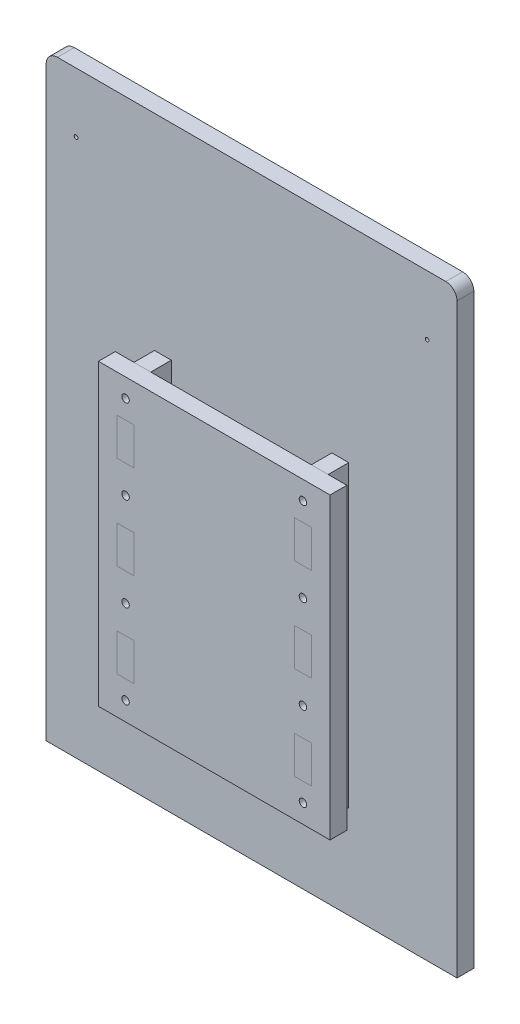
SolidWorks part; units mm, degrees
note: The reader was unsure of these and kept them because the rebuilt part matched: shared geometry of "Model<3>", "Model<4>", "Model<5>", "Model<7>", "Model<8>", "Model<9>".
other "volet-fond"
other "volet_plauqeDessus"
other "voletSupportD"
other "volet-supportG"
ref_plane "Plan de face" through (0, 0, 0) normal (0, 0, 1) x (1, 0, 0)
ref_plane "Plan de dessus" through (0, 0, 0) normal (0, 1, 0) x (1, 0, 0)
ref_plane "Plan de droite" through (0, 0, 0) normal (1, 0, 0) x (0, 0, -1)
sketch "Model" plane through (0, 0, 0) normal (0, 0, 1) x (1, 0, 0)
  line L0 (0, 320) -> (-104, 320)
  line L1 (-110, 314) -> (-110, 0)
  line L2 (-110, 0) -> (0, 0)
  line L3 (0, 0) -> (110, 0)
  line L4 (110, 0) -> (110, 314)
  line L5 (104, 320) -> (0, 320)
  line L6 (-52, 190) -> (-52, 170)
  line L7 (-52, 170) -> (-43, 170)
  line L8 (-43, 170) -> (-43, 190)
  line L9 (-43, 190) -> (-52, 190)
  line L10 (-43, 70) -> (-43, 90)
  line L11 (-43, 90) -> (-52, 90)
  line L12 (-52, 90) -> (-52, 70)
  line L13 (-52, 70) -> (-43, 70)
  line L14 (-52, 120) -> (-43, 120)
  line L15 (-43, 120) -> (-43, 140)
  line L16 (-43, 140) -> (-52, 140)
  line L17 (-52, 140) -> (-52, 120)
  line L18 (47.5, 0) -> (47.5, 320) construction
  line L19 (52, 140) -> (52, 120)
  line L20 (43, 140) -> (52, 140)
  line L21 (43, 120) -> (43, 140)
  line L22 (52, 120) -> (43, 120)
  line L23 (52, 70) -> (43, 70)
  line L24 (52, 90) -> (52, 70)
  line L25 (43, 90) -> (52, 90)
  line L26 (43, 70) -> (43, 90)
  line L27 (43, 190) -> (52, 190)
  line L28 (43, 170) -> (43, 190)
  line L29 (52, 170) -> (43, 170)
  line L30 (0, 0) -> (0, 320) construction
  line L31 (-47.5, 0) -> (-47.5, 320) construction
  line L32 (52, 190) -> (52, 170)
  line L33 (-52, 210) -> (-52, 50)
  line L34 (-62, 210) -> (62, 210)
  line L35 (-62, 210) -> (-62, 50)
  line L36 (-62, 50) -> (62, 50)
  line L37 (62, 210) -> (62, 50)
  line L38 (-43, 210) -> (-43, 50)
  line L39 (43, 210) -> (43, 50)
  line L40 (52, 210) -> (52, 50)
  circle A0 centre (94, 288) radius 1
  circle A1 centre (-94, 288) radius 1
  circle A2 centre (-47.5, 200) radius 2
  circle A3 centre (-47.5, 155) radius 2
  circle A4 centre (-47.5, 105) radius 2
  circle A5 centre (-47.5, 60) radius 2
  circle A6 centre (47.5, 60) radius 2
  circle A7 centre (47.5, 105) radius 2
  circle A8 centre (47.5, 155) radius 2
  circle A9 centre (47.5, 200) radius 2
  arc A10 (-104, 320) -> (-110, 314) centre (-104, 314) ccw
  arc A11 (110, 314) -> (104, 320) centre (104, 314) ccw
  point P61 (-47.5, 90)
  point P62 (-47.5, 120)
  point P65 (0, 50)
  dimension "D6" = 6
  dimension "D7" = 6
  dimension "D12" = 2
  dimension "D15" = 4
  dimension "D1" = 220
  dimension "D2" = 320
  dimension "D3" = 20
  dimension "D4" = 9
  dimension "D5" = 43
  dimension "D8" = 6
  dimension "D9" = 6
  dimension "D10" = 6
  dimension "D11" = 6
  dimension "D13" = 16
  dimension "D14" = 32
  dimension "D16" = 70
  dimension "D17" = 30
  dimension "D18" = 30
  dimension "D19" = 10
  dimension "D20" = 15
  dimension "D21" = 15
  dimension "D22" = 10
  dimension "D23" = 10
  dimension "D24" = 10
  dimension "D25" = 10
extrude "Boss.-Extru.1" add sketch "Model" along normal blind 9 contours L4 A11 L5 L0 A10 L1 L2 L3 A0 L34 L37 L36 L35 A1 | L37 L34 L35 L36 A8 A6 A5 A4 A3 A2 L17 L16 L15 L14 L13 L12 L11 L10 L9 L8 L7 L6 L19 L22 L21 L20 L23 L26 L25 L24 L27 L32 L29 L28 A7 A9 | L35 L36 L33 L12 L17 L6 L34 | L38 L34 L33 L9 A2 | L38 L7 L33 L16 A3 | L38 L14 L33 L11 A4 | L38 L13 L33 L36 A5 | L34 L40 L32 L19 L24 L36 L37 | L40 L23 L39 L36 A6 | L40 L22 L39 L25 A7 | L40 L29 L39 L20 A8 | L40 L34 L39 L27 A9
extrude "Boss.-Extru.3" add sketch "Model<3>" along normal blind 11 from surface at 9 separate body contours L38 L34 L33 L9 A2 | L38 L7 L33 L16 A3 | L38 L14 L33 L11 A4 | L38 L13 L33 L36 A5 | L12 L13 L10 L11 | L16 L17 L14 L15 | L8 L9 L6 L7 | L40 L34 L39 L27 A9 | L32 L27 L28 L29 | L40 L29 L39 L20 A8 | L22 L19 L20 L21 | L40 L22 L39 L25 A7 | L26 L23 L24 L25 | L40 L23 L39 L36 A6 starting at face at (47.5, 180, 9)
sketch "Model<3>" plane through (0, 0, 0) normal (0, 0, 1) x (1, 0, 0) same geometry as "Model"
extrude "Boss.-Extru.4" add sketch "Model<4>" along normal up to surface (9 mm away) contours L8 L9 L6 L7 | L16 L17 L14 L15 | L12 L13 L10 L11
sketch "Model<4>" plane through (0, 0, 0) normal (0, 0, 1) x (1, 0, 0) same geometry as "Model"
extrude "Boss.-Extru.5" add sketch "Model<5>" along normal up to surface (9 mm away) contours L32 L27 L28 L29 | L22 L19 L20 L21 | L26 L23 L24 L25
sketch "Model<5>" plane through (0, 0, 0) normal (0, 0, 1) x (1, 0, 0) same geometry as "Model"
extrude "Boss.-Extru.6" add sketch "Model<7>" along normal blind 9 from surface at 20 separate body contours L35 L36 L33 L12 L17 L6 L34 | L38 L34 L33 L9 A2 | L38 L7 L33 L16 A3 | L38 L14 L33 L11 A4 | L38 L13 L33 L36 A5 | L39 L34 L38 L8 L15 L10 L36 L26 L21 L28 | L40 L34 L39 L27 A9 | L34 L40 L32 L19 L24 L36 L37 | L40 L29 L39 L20 A8 | L40 L22 L39 L25 A7 | L40 L23 L39 L36 A6 starting at face at (-47.5, 130, 20)
sketch "Model<7>" plane through (0, 0, 0) normal (0, 0, 1) x (1, 0, 0) same geometry as "Model"
extrude "Boss.-Extru.7" add sketch "Model<8>" along normal up to surface (9 mm away) from surface at 20 contours L16 L17 L14 L15 | L12 L13 L10 L11 | L8 L9 L6 L7
sketch "Model<8>" plane through (0, 0, 0) normal (0, 0, 1) x (1, 0, 0) same geometry as "Model"
extrude "Boss.-Extru.8" add sketch "Model<9>" along normal up to surface (9 mm away) from surface at 20 contours L32 L27 L28 L29 | L26 L23 L24 L25 | L22 L19 L20 L21
sketch "Model<9>" plane through (0, 0, 0) normal (0, 0, 1) x (1, 0, 0) same geometry as "Model"
other "Enregistrer les corps1"
